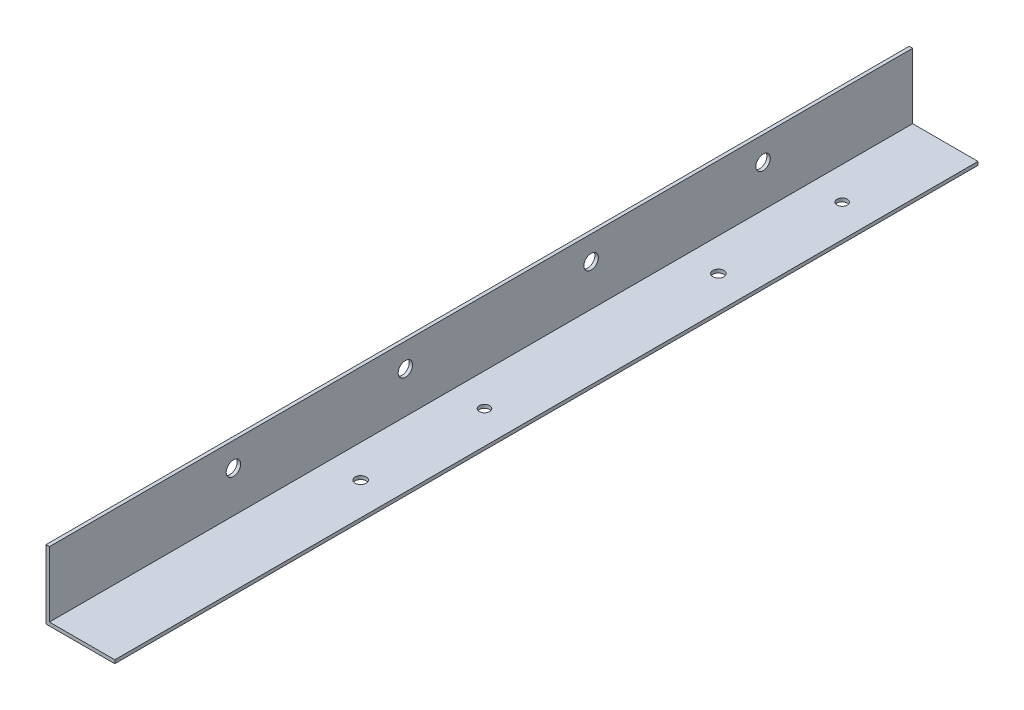
SolidWorks part; units mm, degrees
material "1060 Сплав"
ref_plane "Спереди" through (0, 0, 0) normal (0, 0, 1) x (1, 0, 0)
ref_plane "Сверху" through (0, 0, 0) normal (0, 1, 0) x (1, 0, 0)
ref_plane "Справа" through (0, 0, 0) normal (1, 0, 0) x (0, 0, -1)
sketch "Эскиз1" plane through (0, 0, 0) normal (0, 0, 1) x (1, 0, 0)
  line L0 (0, 0) -> (0, 20)
  line L1 (0, 20) -> (1, 20)
  line L2 (1, 20) -> (1, 1)
  line L3 (1, 1) -> (20, 1)
  line L4 (20, 1) -> (20, 0)
  line L5 (20, 0) -> (0, 0)
  dimension "D1" = 20
  dimension "D2" = 1
extrude "Бобышка-Вытянуть1" add sketch "Эскиз1" along normal blind 251
sketch "Эскиз2" plane through (0, 1, 0) normal (0, 1, 0) x (1, 0, 0)
  line L0 (10.5, 0) -> (10.5, -251) construction
  line L1 (20, 0) -> (1, 0) construction
  line L2 (20, -251) -> (1, -251) construction
ref_plane "Плоскость1" through (10.5, 0, 0) normal (-1, 0, 0) x (0, 0, 1)
sketch "Эскиз3" plane through (0, 1, 0) normal (0, 1, 0) x (1, 0, 0)
  circle A0 centre (10.5, -134) radius 1.5 construction
  circle A1 centre (10.5, -134) radius 1.5
  circle A2 centre (10.5, -170) radius 1.6 construction
  circle A3 centre (10.5, -170) radius 1.6
  circle A4 centre (10.5, -66) radius 1.6 construction
  circle A5 centre (10.5, -66) radius 1.6
  circle A6 centre (10.5, -30) radius 1.5 construction
  circle A7 centre (10.5, -30) radius 1.5
extrude "Вырез-Вытянуть1" cut sketch "Эскиз3" against normal through all
sketch "Эскиз4" plane through (0, 0, 0) normal (-1, 0, 0) x (0, 0, 1)
  line L0 (63.5, 27) -> (63.5, 0) construction
  line L1 (251, 0) -> (0, 0) construction
  line L2 (167.5, 27) -> (167.5, 0) construction
  line L3 (0, 13) -> (251, 13) construction
  line L4 (130, 25) -> (205, 25)
  line L5 (205, 25) -> (205, 27)
  line L6 (205, 27) -> (130, 27)
  line L7 (130, 27) -> (130, 25)
  line L8 (130, 25) -> (205, 25) construction
  line L9 (205, 25) -> (205, 27) construction
  line L10 (205, 27) -> (130, 27) construction
  line L11 (130, 27) -> (130, 25) construction
  line L12 (26, 25) -> (101, 25)
  line L13 (101, 25) -> (101, 27)
  line L14 (101, 27) -> (26, 27)
  line L15 (26, 27) -> (26, 25)
  line L16 (26, 25) -> (101, 25) construction
  line L17 (101, 25) -> (101, 27) construction
  line L18 (101, 27) -> (26, 27) construction
  line L19 (26, 27) -> (26, 25) construction
  line L20 (0, 20) -> (0, 0) construction
  line L21 (251, 20) -> (251, 0) construction
  line L22 (251, 20) -> (0, 20) construction
  circle A0 centre (43.5, 13) radius 2.1
  circle A1 centre (93.5, 13) radius 2.1
  circle A2 centre (147.5, 13) radius 2.1
  circle A3 centre (197.5, 13) radius 2.1
  dimension "D4" = 4.2
  dimension "D5" = 50
  dimension "D6" = 50
  dimension "D8" = 20
  dimension "D3" = 7
  dimension "D7" = 20
  dimension "D1" = 0
  dimension "D2" = 0
extrude "Вырез-Вытянуть2" cut sketch "Эскиз4" against normal through all
